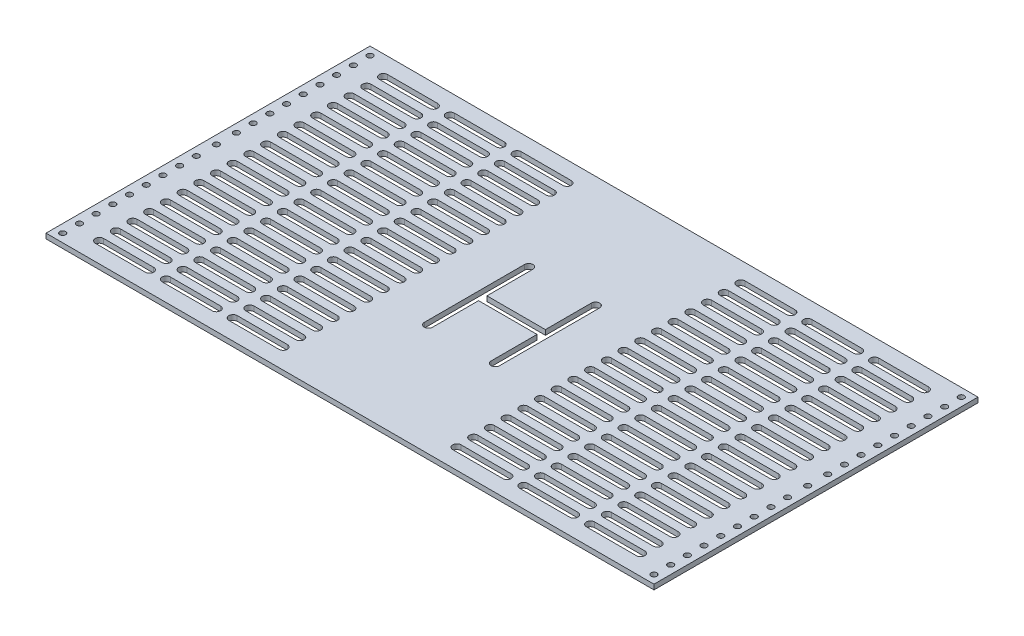
SolidWorks part; units mm, degrees
material "A-玻璃纤维"
ref_plane "前视基准面" through (0, 0, 0) normal (0, 0, 1) x (1, 0, 0)
ref_plane "上视基准面" through (0, 0, 0) normal (0, 1, 0) x (1, 0, 0)
ref_plane "右视基准面" through (0, 0, 0) normal (1, 0, 0) x (0, 0, -1)
other "Configuration Table"
sketch "草图1" plane through (0, 0, 0) normal (0, 1, 0) x (1, 0, 0)
  line L0 (0, 0) -> (-182, 0)
  line L1 (0, 0) -> (182, 0)
  line L2 (182, 0) -> (182, -194)
  line L3 (182, -194) -> (-182, -194)
  line L4 (-182, -194) -> (-182, 0)
  dimension "D1" = 182
extrude "凸台-拉伸1" add sketch "草图1" along normal blind 3
sketch "草图2" plane through (0, 3, 0) normal (0, 1, 0) x (1, 0, 0)
  line L0 (-182, -97) -> (-22.5, -97)
  line L1 (-182, 0) -> (-182, -194) construction
  line L2 (182, -194) -> (182, 0) construction
  line L3 (0, 0) -> (0, -194)
  line L4 (-182, -194) -> (182, -194) construction
  line L5 (0, -97) -> (-20, -97)
  line L6 (0, -97) -> (20, -97)
  line L11 (-20, -97) -> (20, -97) construction
  line L12 (-17.5, -94.5) -> (17.5, -94.5)
  line L13 (-17.5, -99.5) -> (17.5, -99.5)
  line L15 (-22.5, -127) -> (-22.5, -67)
  line L16 (-17.5, -127) -> (-17.5, -99.5)
  line L18 (22.5, -67) -> (22.5, -127)
  line L19 (17.5, -67) -> (17.5, -94.5)
  line L20 (17.5, -99.5) -> (17.5, -127)
  line L21 (-17.5, -94.5) -> (-17.5, -67)
  line L22 (-20, -97) -> (182, -97)
  arc A2 (-22.5, -127) -> (-17.5, -127) centre (-20, -127) ccw
  arc A3 (-17.5, -67) -> (-22.5, -67) centre (-20, -67) ccw
  arc A4 (22.5, -67) -> (17.5, -67) centre (20, -67) ccw
  arc A5 (17.5, -127) -> (22.5, -127) centre (20, -127) ccw
  point P16 (0, -97)
  point P23 (-20, -97)
  point P28 (20, -97)
  dimension "D1" = 20
  dimension "D2" = 20
extrude "切除-拉伸1" cut sketch "草图2" against normal through all and the other way through all contours L20 A5 L18 L22 L6 L3 L13 | L18 A4 L19 L12 L3 L6 L22 | L21 A3 L15 A2 L16 L13 L3 L12 region at (17.5822, 3, 84.1805) region at (-0.6878, 3, 95.75) region at (17.5822, 3, 109.8195)
sketch "草图3" plane through (0, 3, 0) normal (0, 1, 0) x (1, 0, 0)
  line L0 (0, 0) -> (0, -194)
  line L1 (-182, -194) -> (182, -194) construction
  line L2 (-182, -97) -> (182, -97)
  line L3 (-182, 0) -> (-182, -194) construction
  line L4 (182, -194) -> (182, 0) construction
  line L5 (-182, -194) -> (-182, -182)
  line L6 (-182, -182) -> (-172, -182)
  line L7 (-172, -182) -> (-167, -182)
  line L8 (-167, -182) -> (-162, -182)
  line L9 (-162, -182) -> (-132, -182)
  line L10 (-132, -182) -> (-122, -182)
  line L11 (-122, -182) -> (-92, -182)
  line L12 (-92, -182) -> (-82, -182)
  line L13 (-82, -182) -> (-52, -182)
  line L14 (-52, -182) -> (-22, -182)
  line L18 (-162, -182) -> (-132, -182) construction
  line L19 (-162, -179.5) -> (-132, -179.5)
  line L20 (-162, -184.5) -> (-132, -184.5)
  line L21 (-122, -182) -> (-92, -182) construction
  line L22 (-122, -179.5) -> (-92, -179.5)
  line L23 (-122, -184.5) -> (-92, -184.5)
  line L24 (-82, -182) -> (-52, -182) construction
  line L25 (-82, -179.5) -> (-52, -179.5)
  line L26 (-82, -184.5) -> (-52, -184.5)
  line L37 (-162, -174.5) -> (-132, -174.5)
  line L38 (-162, -169.5) -> (-132, -169.5)
  line L47 (-122, -174.5) -> (-92, -174.5)
  line L48 (-122, -169.5) -> (-92, -169.5)
  line L49 (-82, -174.5) -> (-52, -174.5)
  line L50 (-82, -169.5) -> (-52, -169.5)
  line L60 (-162, -172) -> (-132, -172) construction
  line L61 (-122, -172) -> (-92, -172) construction
  line L62 (-82, -172) -> (-52, -172) construction
  line L73 (-162, -164.5) -> (-132, -164.5)
  line L74 (-162, -159.5) -> (-132, -159.5)
  line L83 (-122, -164.5) -> (-92, -164.5)
  line L84 (-122, -159.5) -> (-92, -159.5)
  line L85 (-82, -164.5) -> (-52, -164.5)
  line L86 (-82, -159.5) -> (-52, -159.5)
  line L96 (-162, -162) -> (-132, -162) construction
  line L97 (-122, -162) -> (-92, -162) construction
  line L98 (-82, -162) -> (-52, -162) construction
  line L109 (-162, -154.5) -> (-132, -154.5)
  line L110 (-162, -149.5) -> (-132, -149.5)
  line L119 (-122, -154.5) -> (-92, -154.5)
  line L120 (-122, -149.5) -> (-92, -149.5)
  line L121 (-82, -154.5) -> (-52, -154.5)
  line L122 (-82, -149.5) -> (-52, -149.5)
  line L132 (-162, -152) -> (-132, -152) construction
  line L133 (-122, -152) -> (-92, -152) construction
  line L134 (-82, -152) -> (-52, -152) construction
  line L145 (-162, -144.5) -> (-132, -144.5)
  line L146 (-162, -139.5) -> (-132, -139.5)
  line L155 (-122, -144.5) -> (-92, -144.5)
  line L156 (-122, -139.5) -> (-92, -139.5)
  line L157 (-82, -144.5) -> (-52, -144.5)
  line L158 (-82, -139.5) -> (-52, -139.5)
  line L168 (-162, -142) -> (-132, -142) construction
  line L169 (-122, -142) -> (-92, -142) construction
  line L170 (-82, -142) -> (-52, -142) construction
  line L181 (-162, -134.5) -> (-132, -134.5)
  line L182 (-162, -129.5) -> (-132, -129.5)
  line L191 (-122, -134.5) -> (-92, -134.5)
  line L192 (-122, -129.5) -> (-92, -129.5)
  line L193 (-82, -134.5) -> (-52, -134.5)
  line L194 (-82, -129.5) -> (-52, -129.5)
  line L204 (-162, -132) -> (-132, -132) construction
  line L205 (-122, -132) -> (-92, -132) construction
  line L206 (-82, -132) -> (-52, -132) construction
  line L217 (-162, -124.5) -> (-132, -124.5)
  line L218 (-162, -119.5) -> (-132, -119.5)
  line L227 (-122, -124.5) -> (-92, -124.5)
  line L228 (-122, -119.5) -> (-92, -119.5)
  line L229 (-82, -124.5) -> (-52, -124.5)
  line L230 (-82, -119.5) -> (-52, -119.5)
  line L232 (-162, -122) -> (-132, -122) construction
  line L233 (-122, -122) -> (-92, -122) construction
  line L234 (-82, -122) -> (-52, -122) construction
  line L237 (-162, -114.5) -> (-132, -114.5)
  line L238 (-162, -109.5) -> (-132, -109.5)
  line L239 (-122, -114.5) -> (-92, -114.5)
  line L240 (-122, -109.5) -> (-92, -109.5)
  line L241 (-82, -114.5) -> (-52, -114.5)
  line L242 (-82, -109.5) -> (-52, -109.5)
  line L244 (-162, -112) -> (-132, -112) construction
  line L245 (-122, -112) -> (-92, -112) construction
  line L246 (-82, -112) -> (-52, -112) construction
  line L249 (-162, -104.5) -> (-132, -104.5)
  line L250 (-162, -99.5) -> (-132, -99.5)
  line L251 (-122, -104.5) -> (-92, -104.5)
  line L252 (-122, -99.5) -> (-92, -99.5)
  line L253 (-82, -104.5) -> (-52, -104.5)
  line L254 (-82, -99.5) -> (-52, -99.5)
  line L256 (-162, -102) -> (-132, -102) construction
  line L257 (-122, -102) -> (-92, -102) construction
  line L258 (-82, -102) -> (-52, -102) construction
  line L261 (-162, -94.5) -> (-132, -94.5)
  line L262 (-162, -89.5) -> (-132, -89.5)
  line L263 (-122, -94.5) -> (-92, -94.5)
  line L264 (-122, -89.5) -> (-92, -89.5)
  line L265 (-82, -94.5) -> (-52, -94.5)
  line L266 (-82, -89.5) -> (-52, -89.5)
  line L268 (-162, -92) -> (-132, -92) construction
  line L269 (-122, -92) -> (-92, -92) construction
  line L270 (-82, -92) -> (-52, -92) construction
  line L273 (-162, -84.5) -> (-132, -84.5)
  line L274 (-162, -79.5) -> (-132, -79.5)
  line L275 (-122, -84.5) -> (-92, -84.5)
  line L276 (-122, -79.5) -> (-92, -79.5)
  line L277 (-82, -84.5) -> (-52, -84.5)
  line L278 (-82, -79.5) -> (-52, -79.5)
  line L280 (-162, -82) -> (-132, -82) construction
  line L281 (-122, -82) -> (-92, -82) construction
  line L282 (-82, -82) -> (-52, -82) construction
  line L285 (-162, -74.5) -> (-132, -74.5)
  line L286 (-162, -69.5) -> (-132, -69.5)
  line L287 (-122, -74.5) -> (-92, -74.5)
  line L288 (-122, -69.5) -> (-92, -69.5)
  line L289 (-82, -74.5) -> (-52, -74.5)
  line L290 (-82, -69.5) -> (-52, -69.5)
  line L292 (-162, -72) -> (-132, -72) construction
  line L293 (-122, -72) -> (-92, -72) construction
  line L294 (-82, -72) -> (-52, -72) construction
  line L297 (-162, -64.5) -> (-132, -64.5)
  line L298 (-162, -59.5) -> (-132, -59.5)
  line L299 (-122, -64.5) -> (-92, -64.5)
  line L300 (-122, -59.5) -> (-92, -59.5)
  line L301 (-82, -64.5) -> (-52, -64.5)
  line L302 (-82, -59.5) -> (-52, -59.5)
  line L304 (-162, -62) -> (-132, -62) construction
  line L305 (-122, -62) -> (-92, -62) construction
  line L306 (-82, -62) -> (-52, -62) construction
  line L309 (-162, -54.5) -> (-132, -54.5)
  line L310 (-162, -49.5) -> (-132, -49.5)
  line L311 (-122, -54.5) -> (-92, -54.5)
  line L312 (-122, -49.5) -> (-92, -49.5)
  line L313 (-82, -54.5) -> (-52, -54.5)
  line L314 (-82, -49.5) -> (-52, -49.5)
  line L316 (-162, -52) -> (-132, -52) construction
  line L317 (-122, -52) -> (-92, -52) construction
  line L318 (-82, -52) -> (-52, -52) construction
  line L321 (-162, -44.5) -> (-132, -44.5)
  line L322 (-162, -39.5) -> (-132, -39.5)
  line L323 (-122, -44.5) -> (-92, -44.5)
  line L324 (-122, -39.5) -> (-92, -39.5)
  line L325 (-82, -44.5) -> (-52, -44.5)
  line L326 (-82, -39.5) -> (-52, -39.5)
  line L328 (-162, -42) -> (-132, -42) construction
  line L329 (-122, -42) -> (-92, -42) construction
  line L330 (-82, -42) -> (-52, -42) construction
  line L333 (-162, -34.5) -> (-132, -34.5)
  line L334 (-162, -29.5) -> (-132, -29.5)
  line L335 (-122, -34.5) -> (-92, -34.5)
  line L336 (-122, -29.5) -> (-92, -29.5)
  line L337 (-82, -34.5) -> (-52, -34.5)
  line L338 (-82, -29.5) -> (-52, -29.5)
  line L340 (-162, -32) -> (-132, -32) construction
  line L341 (-122, -32) -> (-92, -32) construction
  line L342 (-82, -32) -> (-52, -32) construction
  line L345 (-162, -24.5) -> (-132, -24.5)
  line L346 (-162, -19.5) -> (-132, -19.5)
  line L347 (-122, -24.5) -> (-92, -24.5)
  line L348 (-122, -19.5) -> (-92, -19.5)
  line L349 (-82, -24.5) -> (-52, -24.5)
  line L350 (-82, -19.5) -> (-52, -19.5)
  line L352 (-162, -22) -> (-132, -22) construction
  line L353 (-122, -22) -> (-92, -22) construction
  line L354 (-82, -22) -> (-52, -22) construction
  line L357 (-162, -14.5) -> (-132, -14.5)
  line L358 (-162, -9.5) -> (-132, -9.5)
  line L359 (-122, -14.5) -> (-92, -14.5)
  line L360 (-122, -9.5) -> (-92, -9.5)
  line L361 (-82, -14.5) -> (-52, -14.5)
  line L362 (-82, -9.5) -> (-52, -9.5)
  line L364 (-162, -12) -> (-132, -12) construction
  line L365 (-122, -12) -> (-92, -12) construction
  line L366 (-82, -12) -> (-52, -12) construction
  arc A2 (-162, -179.5) -> (-162, -184.5) centre (-162, -182) ccw
  arc A3 (-132, -184.5) -> (-132, -179.5) centre (-132, -182) ccw
  arc A4 (-122, -179.5) -> (-122, -184.5) centre (-122, -182) ccw
  arc A5 (-92, -184.5) -> (-92, -179.5) centre (-92, -182) ccw
  arc A6 (-82, -179.5) -> (-82, -184.5) centre (-82, -182) ccw
  arc A7 (-52, -184.5) -> (-52, -179.5) centre (-52, -182) ccw
  arc A146 (-162, -169.5) -> (-162, -174.5) centre (-162, -172) ccw
  arc A147 (-132, -174.5) -> (-132, -169.5) centre (-132, -172) ccw
  arc A148 (-122, -169.5) -> (-122, -174.5) centre (-122, -172) ccw
  arc A149 (-92, -174.5) -> (-92, -169.5) centre (-92, -172) ccw
  arc A150 (-82, -169.5) -> (-82, -174.5) centre (-82, -172) ccw
  arc A151 (-52, -174.5) -> (-52, -169.5) centre (-52, -172) ccw
  arc A154 (-162, -159.5) -> (-162, -164.5) centre (-162, -162) ccw
  arc A155 (-132, -164.5) -> (-132, -159.5) centre (-132, -162) ccw
  arc A156 (-122, -159.5) -> (-122, -164.5) centre (-122, -162) ccw
  arc A157 (-92, -164.5) -> (-92, -159.5) centre (-92, -162) ccw
  arc A158 (-82, -159.5) -> (-82, -164.5) centre (-82, -162) ccw
  arc A159 (-52, -164.5) -> (-52, -159.5) centre (-52, -162) ccw
  arc A162 (-162, -149.5) -> (-162, -154.5) centre (-162, -152) ccw
  arc A163 (-132, -154.5) -> (-132, -149.5) centre (-132, -152) ccw
  arc A164 (-122, -149.5) -> (-122, -154.5) centre (-122, -152) ccw
  arc A165 (-92, -154.5) -> (-92, -149.5) centre (-92, -152) ccw
  arc A166 (-82, -149.5) -> (-82, -154.5) centre (-82, -152) ccw
  arc A167 (-52, -154.5) -> (-52, -149.5) centre (-52, -152) ccw
  arc A170 (-162, -139.5) -> (-162, -144.5) centre (-162, -142) ccw
  arc A171 (-132, -144.5) -> (-132, -139.5) centre (-132, -142) ccw
  arc A172 (-122, -139.5) -> (-122, -144.5) centre (-122, -142) ccw
  arc A173 (-92, -144.5) -> (-92, -139.5) centre (-92, -142) ccw
  arc A174 (-82, -139.5) -> (-82, -144.5) centre (-82, -142) ccw
  arc A175 (-52, -144.5) -> (-52, -139.5) centre (-52, -142) ccw
  arc A178 (-162, -129.5) -> (-162, -134.5) centre (-162, -132) ccw
  arc A179 (-132, -134.5) -> (-132, -129.5) centre (-132, -132) ccw
  arc A180 (-122, -129.5) -> (-122, -134.5) centre (-122, -132) ccw
  arc A181 (-92, -134.5) -> (-92, -129.5) centre (-92, -132) ccw
  arc A182 (-82, -129.5) -> (-82, -134.5) centre (-82, -132) ccw
  arc A183 (-52, -134.5) -> (-52, -129.5) centre (-52, -132) ccw
  arc A186 (-162, -119.5) -> (-162, -124.5) centre (-162, -122) ccw
  arc A187 (-132, -124.5) -> (-132, -119.5) centre (-132, -122) ccw
  arc A188 (-122, -119.5) -> (-122, -124.5) centre (-122, -122) ccw
  arc A189 (-92, -124.5) -> (-92, -119.5) centre (-92, -122) ccw
  arc A190 (-82, -119.5) -> (-82, -124.5) centre (-82, -122) ccw
  arc A191 (-52, -124.5) -> (-52, -119.5) centre (-52, -122) ccw
  arc A194 (-162, -109.5) -> (-162, -114.5) centre (-162, -112) ccw
  arc A195 (-132, -114.5) -> (-132, -109.5) centre (-132, -112) ccw
  arc A196 (-122, -109.5) -> (-122, -114.5) centre (-122, -112) ccw
  arc A197 (-92, -114.5) -> (-92, -109.5) centre (-92, -112) ccw
  arc A198 (-82, -109.5) -> (-82, -114.5) centre (-82, -112) ccw
  arc A199 (-52, -114.5) -> (-52, -109.5) centre (-52, -112) ccw
  arc A202 (-162, -99.5) -> (-162, -104.5) centre (-162, -102) ccw
  arc A203 (-132, -104.5) -> (-132, -99.5) centre (-132, -102) ccw
  arc A204 (-122, -99.5) -> (-122, -104.5) centre (-122, -102) ccw
  arc A205 (-92, -104.5) -> (-92, -99.5) centre (-92, -102) ccw
  arc A206 (-82, -99.5) -> (-82, -104.5) centre (-82, -102) ccw
  arc A207 (-52, -104.5) -> (-52, -99.5) centre (-52, -102) ccw
  arc A210 (-162, -89.5) -> (-162, -94.5) centre (-162, -92) ccw
  arc A211 (-132, -94.5) -> (-132, -89.5) centre (-132, -92) ccw
  arc A212 (-122, -89.5) -> (-122, -94.5) centre (-122, -92) ccw
  arc A213 (-92, -94.5) -> (-92, -89.5) centre (-92, -92) ccw
  arc A214 (-82, -89.5) -> (-82, -94.5) centre (-82, -92) ccw
  arc A215 (-52, -94.5) -> (-52, -89.5) centre (-52, -92) ccw
  arc A218 (-162, -79.5) -> (-162, -84.5) centre (-162, -82) ccw
  arc A219 (-132, -84.5) -> (-132, -79.5) centre (-132, -82) ccw
  arc A220 (-122, -79.5) -> (-122, -84.5) centre (-122, -82) ccw
  arc A221 (-92, -84.5) -> (-92, -79.5) centre (-92, -82) ccw
  arc A222 (-82, -79.5) -> (-82, -84.5) centre (-82, -82) ccw
  arc A223 (-52, -84.5) -> (-52, -79.5) centre (-52, -82) ccw
  arc A226 (-162, -69.5) -> (-162, -74.5) centre (-162, -72) ccw
  arc A227 (-132, -74.5) -> (-132, -69.5) centre (-132, -72) ccw
  arc A228 (-122, -69.5) -> (-122, -74.5) centre (-122, -72) ccw
  arc A229 (-92, -74.5) -> (-92, -69.5) centre (-92, -72) ccw
  arc A230 (-82, -69.5) -> (-82, -74.5) centre (-82, -72) ccw
  arc A231 (-52, -74.5) -> (-52, -69.5) centre (-52, -72) ccw
  arc A234 (-162, -59.5) -> (-162, -64.5) centre (-162, -62) ccw
  arc A235 (-132, -64.5) -> (-132, -59.5) centre (-132, -62) ccw
  arc A236 (-122, -59.5) -> (-122, -64.5) centre (-122, -62) ccw
  arc A237 (-92, -64.5) -> (-92, -59.5) centre (-92, -62) ccw
  arc A238 (-82, -59.5) -> (-82, -64.5) centre (-82, -62) ccw
  arc A239 (-52, -64.5) -> (-52, -59.5) centre (-52, -62) ccw
  arc A242 (-162, -49.5) -> (-162, -54.5) centre (-162, -52) ccw
  arc A243 (-132, -54.5) -> (-132, -49.5) centre (-132, -52) ccw
  arc A244 (-122, -49.5) -> (-122, -54.5) centre (-122, -52) ccw
  arc A245 (-92, -54.5) -> (-92, -49.5) centre (-92, -52) ccw
  arc A246 (-82, -49.5) -> (-82, -54.5) centre (-82, -52) ccw
  arc A247 (-52, -54.5) -> (-52, -49.5) centre (-52, -52) ccw
  arc A250 (-162, -39.5) -> (-162, -44.5) centre (-162, -42) ccw
  arc A251 (-132, -44.5) -> (-132, -39.5) centre (-132, -42) ccw
  arc A252 (-122, -39.5) -> (-122, -44.5) centre (-122, -42) ccw
  arc A253 (-92, -44.5) -> (-92, -39.5) centre (-92, -42) ccw
  arc A254 (-82, -39.5) -> (-82, -44.5) centre (-82, -42) ccw
  arc A255 (-52, -44.5) -> (-52, -39.5) centre (-52, -42) ccw
  arc A258 (-162, -29.5) -> (-162, -34.5) centre (-162, -32) ccw
  arc A259 (-132, -34.5) -> (-132, -29.5) centre (-132, -32) ccw
  arc A260 (-122, -29.5) -> (-122, -34.5) centre (-122, -32) ccw
  arc A261 (-92, -34.5) -> (-92, -29.5) centre (-92, -32) ccw
  arc A262 (-82, -29.5) -> (-82, -34.5) centre (-82, -32) ccw
  arc A263 (-52, -34.5) -> (-52, -29.5) centre (-52, -32) ccw
  arc A266 (-162, -19.5) -> (-162, -24.5) centre (-162, -22) ccw
  arc A267 (-132, -24.5) -> (-132, -19.5) centre (-132, -22) ccw
  arc A268 (-122, -19.5) -> (-122, -24.5) centre (-122, -22) ccw
  arc A269 (-92, -24.5) -> (-92, -19.5) centre (-92, -22) ccw
  arc A270 (-82, -19.5) -> (-82, -24.5) centre (-82, -22) ccw
  arc A271 (-52, -24.5) -> (-52, -19.5) centre (-52, -22) ccw
  arc A274 (-162, -9.5) -> (-162, -14.5) centre (-162, -12) ccw
  arc A275 (-132, -14.5) -> (-132, -9.5) centre (-132, -12) ccw
  arc A276 (-122, -9.5) -> (-122, -14.5) centre (-122, -12) ccw
  arc A277 (-92, -14.5) -> (-92, -9.5) centre (-92, -12) ccw
  arc A278 (-82, -9.5) -> (-82, -14.5) centre (-82, -12) ccw
  arc A279 (-52, -14.5) -> (-52, -9.5) centre (-52, -12) ccw
  point P28 (-147, -182)
  point P33 (-107, -182)
  point P38 (-67, -182)
  point P58 (-147, -172)
  point P63 (-107, -172)
  point P68 (-67, -172)
  point P86 (-147, -162)
  point P91 (-107, -162)
  point P96 (-67, -162)
  point P114 (-147, -152)
  point P119 (-107, -152)
  point P124 (-67, -152)
  point P142 (-147, -142)
  point P147 (-107, -142)
  point P152 (-67, -142)
  point P170 (-147, -132)
  point P175 (-107, -132)
  point P180 (-67, -132)
  point P198 (-147, -122)
  point P203 (-107, -122)
  point P208 (-67, -122)
  point P226 (-147, -112)
  point P231 (-107, -112)
  point P236 (-67, -112)
  point P254 (-147, -102)
  point P259 (-107, -102)
  point P264 (-67, -102)
  point P282 (-147, -92)
  point P287 (-107, -92)
  point P292 (-67, -92)
  point P310 (-147, -82)
  point P315 (-107, -82)
  point P320 (-67, -82)
  point P338 (-147, -72)
  point P343 (-107, -72)
  point P348 (-67, -72)
  point P366 (-147, -62)
  point P371 (-107, -62)
  point P376 (-67, -62)
  point P394 (-147, -52)
  point P399 (-107, -52)
  point P404 (-67, -52)
  point P422 (-147, -42)
  point P427 (-107, -42)
  point P432 (-67, -42)
  point P450 (-147, -32)
  point P455 (-107, -32)
  point P460 (-67, -32)
  point P478 (-147, -22)
  point P483 (-107, -22)
  point P488 (-67, -22)
  point P506 (-147, -12)
  point P511 (-107, -12)
  point P516 (-67, -12)
  dimension "D1" = 12
  dimension "D3" = 18
  dimension "D2" = 10
  dimension "D4" = 5
  dimension "D5" = 5
  dimension "D6" = 30
  dimension "D7" = 10
  dimension "D8" = 30
  dimension "D9" = 10
  dimension "D10" = 30
extrude "切除-拉伸2" cut sketch "草图3" against normal through all contours L8 L7 L6 | L8 L6 L7 | L20 A3 L10 L9 L8 A2 | L10 A3 L19 A2 L8 L9 | L23 A5 L12 L11 L10 A4 | L12 A5 L22 A4 L10 L11 | L26 A7 L14 L13 L12 A6 | L14 A7 L25 A6 L12 L13 | L49 A151 L50 A150 | L47 A149 L48 A148 | L37 A147 L38 A146 | L73 A155 L74 A154 | L83 A157 L84 A156 | L85 A159 L86 A158 | L121 A167 L122 A166 | L119 A165 L120 A164 | L109 A163 L110 A162 | L157 A175 L158 A174 | L155 A173 L156 A172 | L145 A171 L146 A170 | L181 A179 L182 A178 | L191 A181 L192 A180 | L193 A183 L194 A182 | L229 A191 L230 A190 | L227 A189 L228 A188 | L217 A187 L218 A186 | L241 A199 L242 A198 | L239 A197 L240 A196 | L237 A195 L238 A194 | L249 A203 L250 A202 | L251 A205 L252 A204 | L253 A207 L254 A206 region at (-147, 3, 180.7719) region at (-67, 3, 180.7719) region at (-67, 3, 183.2281) region at (-107, 3, 180.7719) region at (-107, 3, 183.2281) region at (-147, 3, 183.2281) region at (-147, 3, 172) region at (-107, 3, 172) region at (-67, 3, 172) region at (-147, 3, 162) region at (-107, 3, 162) region at (-67, 3, 162) region at (-147, 3, 152) region at (-107, 3, 152) region at (-67, 3, 152) region at (-147, 3, 142) region at (-107, 3, 142) region at (-67, 3, 142) region at (-147, 3, 132) region at (-107, 3, 132) region at (-67, 3, 132) region at (-147, 3, 122) region at (-107, 3, 122) region at (-67, 3, 122) region at (-147, 3, 112) region at (-107, 3, 112) region at (-67, 3, 112) region at (-147, 3, 102) region at (-107, 3, 102) region at (-67, 3, 102)
ref_plane "基准面1" through (0, 0, 97) normal (0, 0, 1) x (1, 0, 0)
mirror "镜向1" about plane through (0, 0, 97) normal (0, 0, 1) of "切除-拉伸2"
mirror "镜向2" about plane through (0, 0, 0) normal (1, 0, 0) of "镜向1"
sketch "草图4" plane through (0, 3, 0) normal (0, 1, 0) x (1, 0, 0)
  line L0 (-182, -194) -> (-177, -194)
  line L1 (-182, -194) -> (182, -194) construction
  line L2 (-177, -194) -> (-177, -189)
  circle A0 centre (-177, -189) radius 1.75
  circle A1 centre (-177, -179) radius 1.75
  circle A2 centre (-177, -169) radius 1.75
  circle A3 centre (-177, -159) radius 1.75
  circle A4 centre (-177, -149) radius 1.75
  circle A5 centre (-177, -139) radius 1.75
  circle A6 centre (-177, -129) radius 1.75
  circle A7 centre (-177, -119) radius 1.75
  circle A8 centre (-177, -109) radius 1.75
  circle A9 centre (-177, -99) radius 1.75
  circle A10 centre (-177, -89) radius 1.75
  circle A11 centre (-177, -79) radius 1.75
  circle A12 centre (-177, -69) radius 1.75
  circle A13 centre (-177, -59) radius 1.75
  circle A14 centre (-177, -49) radius 1.75
  circle A15 centre (-177, -39) radius 1.75
  circle A16 centre (-177, -29) radius 1.75
  circle A17 centre (-177, -19) radius 1.75
  circle A18 centre (-177, -9) radius 1.75
  dimension "D3" = 19
  dimension "D1" = 5
  dimension "D2" = 5
extrude "切除-拉伸3" cut sketch "草图4" against normal through all contours A0 | A1 | A2 | A3 | A4 | A5 | A6 | A7 | A8 region at (-175.7976, 3, 190.2024) region at (-177, 3, 179) region at (-177, 3, 169) region at (-177, 3, 159) region at (-177, 3, 149) region at (-177, 3, 139) region at (-177, 3, 129) region at (-177, 3, 119) region at (-177, 3, 109)
mirror "镜向3" about plane through (0, 0, 97) normal (0, 0, 1) of "切除-拉伸3"
sketch "草图5" plane through (0, 3, 0) normal (0, 1, 0) x (1, 0, 0)
  line L0 (-177, -109) -> (-177, -85)
  line L1 (-177, -109) -> (-177, -97)
  circle A0 centre (-177, -97) radius 1.75
extrude "切除-拉伸4" cut sketch "草图5" against normal through all contours L1 A0 L0 | L0 A0 L1 region at (-177.7427, 3, 97) region at (-176.2573, 3, 97)
mirror "镜向4" about plane through (0, 0, 0) normal (1, 0, 0) of "镜向3", "切除-拉伸4", "切除-拉伸3"
